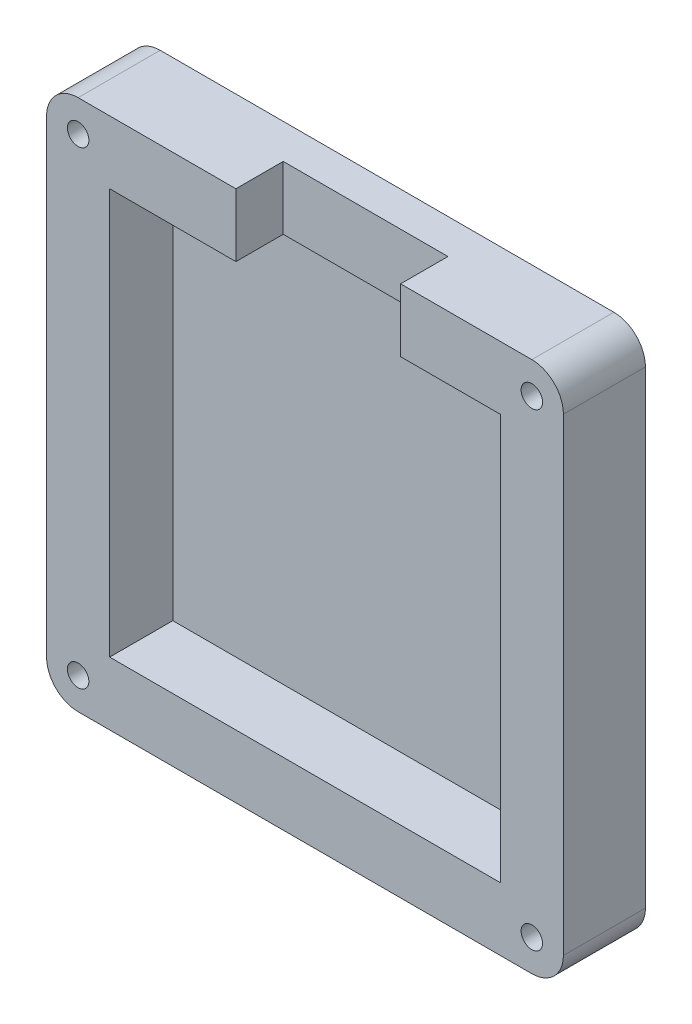
SolidWorks part; units mm, degrees
ref_plane "Front Plane" through (0, 0, 0) normal (0, 0, 1) x (1, 0, 0)
ref_plane "Top Plane" through (0, 0, 0) normal (0, 1, 0) x (1, 0, 0)
ref_plane "Right Plane" through (0, 0, 0) normal (1, 0, 0) x (0, 0, -1)
sketch "Sketch2" plane through (0, 0, 0) normal (0, 0, 1) x (1, 0, 0)
  line L1 (30.9465, 32.1375) -> (-30.9465, 32.1375)
  line L2 (30.9465, 32.1375) -> (30.9465, -32.1375)
  line L3 (30.9465, -32.1375) -> (-30.9465, -32.1375)
  line L4 (-30.9465, 32.1375) -> (-30.9465, -32.1375)
  line L5 (30.9465, 32.1375) -> (-30.9465, -32.1375) construction
  line L6 (30.9465, -32.1375) -> (-30.9465, 32.1375) construction
  line L7 (-40.9465, 42.1375) -> (40.9465, 42.1375)
  line L8 (-40.9465, 42.1375) -> (-40.9465, -42.1375)
  line L9 (-40.9465, -42.1375) -> (40.9465, -42.1375)
  line L10 (40.9465, 42.1375) -> (40.9465, -42.1375)
  circle A5 centre (35.9465, 37.1375) radius 1.7
  circle A6 centre (-35.9465, -37.1375) radius 1.7
  circle A7 centre (35.9465, -37.1375) radius 1.7
  circle A8 centre (-35.9465, 37.1375) radius 1.7
  circle A9 centre (-35.9465, 37.1375) radius 3
  circle A10 centre (35.9465, 37.1375) radius 3
  circle A11 centre (-35.9465, -37.1375) radius 3
  circle A12 centre (35.9465, -37.1375) radius 3
  point P0 (0, 0)
  dimension "D8" = 5
  dimension "D9" = 3.4
  dimension "D10" = 5
  dimension "D12" = 3.4
  dimension "D13" = 3.4
  dimension "D14" = 5
  dimension "D15" = 5
  dimension "D16" = 3.4
  dimension "D17" = 5
  dimension "D18" = 5
  dimension "D19" = 6
  dimension "D20" = 6
  dimension "D21" = 6
  dimension "D22" = 6
  dimension "D1" = 61.893
  dimension "D2" = 64.275
  dimension "D3" = 10
  dimension "D4" = 10
  dimension "D5" = 10
  dimension "D6" = 10
  dimension "D7" = 5
  dimension "D11" = 5
  dimension "D23" = 81.893
  dimension "D24" = 84.275
extrude "Boss-Extrude4" add sketch "Sketch2" along normal blind 9.9 from offset 3.1 contours A5 | A10 | A9 | A6 | A11 | A7 | A12 | A8
extrude "Boss-Extrude5" add sketch "Sketch2<12>" along normal blind 13 contours L10 L7 L8 L9 A12 A11 A10 A9 L4 L1 L2 L3 region at (0, 40.9624, 0)
sketch "Sketch2<12>" plane through (0, 0, 0) normal (0, 0, 1) x (1, 0, 0) same geometry as "Sketch2"
extrude "Boss-Extrude6" add sketch "Sketch2<13>" along normal blind 3 contours L1 L4 L3 L2 region at (0, 0, 0)
sketch "Sketch2<13>" plane through (0, 0, 0) normal (0, 0, 1) x (1, 0, 0) same geometry as "Sketch2"
sketch "Sketch5" plane through (0, 0, 13) normal (0, 0, 1) x (1, 0, 0)
  line L0 (-40.9465, 42.1375) -> (40.9465, 42.1375) construction
  line L1 (-10.9465, 42.1375) -> (15.1513, 42.1375)
  line L2 (-10.9465, 42.1375) -> (-10.9465, 32.1375)
  line L3 (-10.9465, 32.1375) -> (15.1513, 32.1375)
  line L4 (15.1513, 42.1375) -> (15.1513, 32.1375)
  line L5 (30.9465, 32.1375) -> (-30.9465, 32.1375) construction
  line L6 (-30.9465, 32.1375) -> (-30.9465, -32.1375) construction
  dimension "D1" = 26.0978
  dimension "D2" = 20
extrude "Cut-Extrude1" cut sketch "Sketch5" against normal blind 7.5 contours L2 L3 L4 L1
fillet "Fillet1" radius 5 4 edges at (-40.9465, -42.1375, 6.5) (-40.9465, 42.1375, 6.5) (40.9465, -42.1375, 6.5) (40.9465, 42.1375, 6.5)
sketch "Sketch7" plane through (0, 0, 0) normal (0, 0, -1) x (-1, 0, 0)
  text T0 "darsh's tetrios" font "Century Gothic" height in points 8
  dimension "D1" = 0
extrude "Cut-Extrude2" cut sketch "Sketch7" against normal blind 0.2
